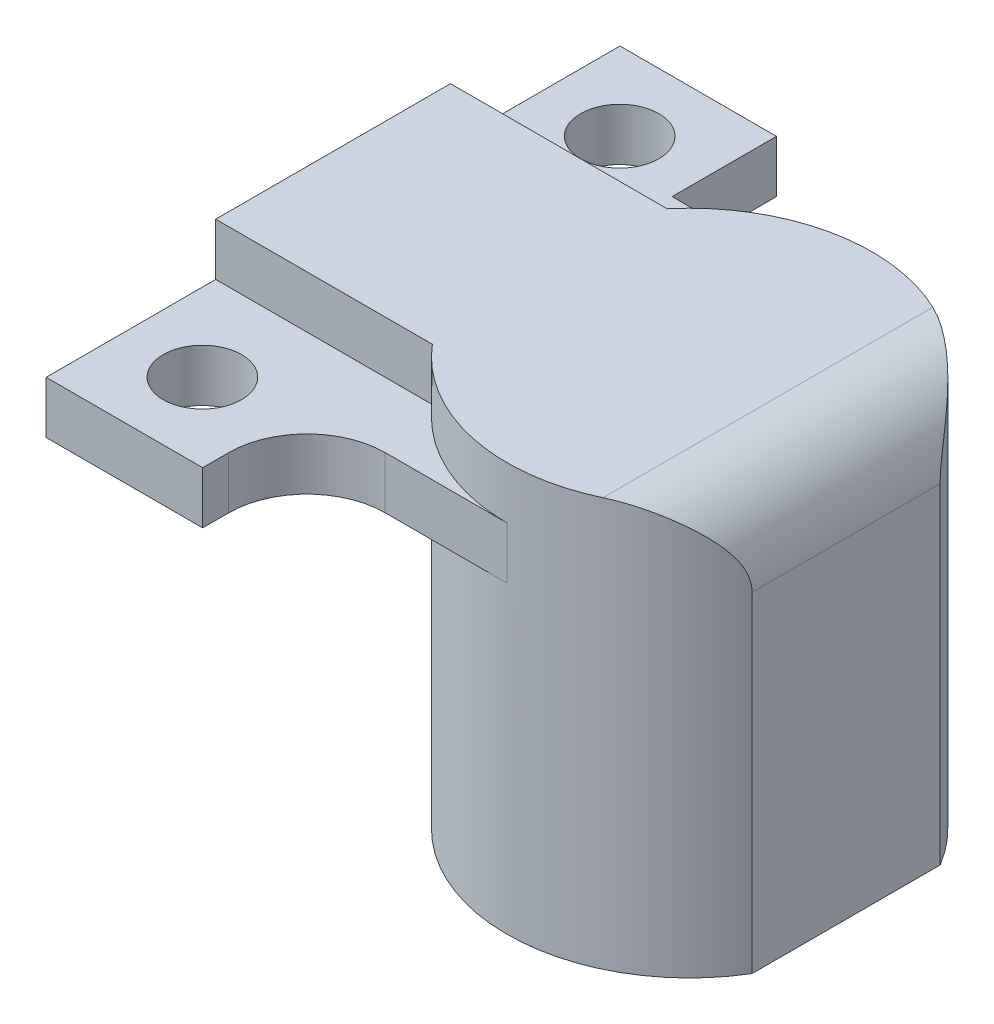
SolidWorks part; units mm, degrees
material "Copper"
ref_plane "Front Plane" through (0, 0, 0) normal (0, 0, 1) x (1, 0, 0)
ref_plane "Top Plane" through (0, 0, 0) normal (0, 1, 0) x (1, 0, 0)
ref_plane "Right Plane" through (0, 0, 0) normal (1, 0, 0) x (0, 0, -1)
sketch "Sketch1" plane through (0, 0, 0) normal (0, 1, 0) x (1, 0, 0)
  circle A0 centre (0, 0) radius 5.2
  circle A1 centre (0, 0) radius 7
  dimension "D1" = 10.4
  dimension "D2" = 14
extrude "Boss-Extrude1" add sketch "Sketch1" along normal blind 15.66
sketch "Sketch2" plane through (0, 15.66, 0) normal (0, 1, 0) x (1, 0, 0)
  line L0 (0, 0) -> (-6.5789, 0) construction
  line L1 (0, 5.2) -> (0, 7)
  line L2 (-13.67, -7) -> (0, -7)
  line L3 (-13.67, -7) -> (-13.67, 7)
  line L4 (-13.67, 7) -> (0, 7)
  line L5 (0, -7) -> (0, -5.2)
  line L6 (-13.67, -7) -> (0, 7) construction
  line L7 (-13.67, 7) -> (0, -7) construction
  line L8 (-7.67, 7) -> (-7.67, 11)
  line L9 (-13.67, -7) -> (-7.67, -7)
  line L10 (-13.67, -7) -> (-13.67, -11)
  line L11 (-13.67, -11) -> (-7.67, -11)
  line L12 (-7.67, -7) -> (-7.67, -11)
  line L13 (-13.67, 11) -> (-7.67, 11)
  line L14 (-13.67, 7) -> (-13.67, 11)
  line L15 (-13.67, 7) -> (-7.67, 7)
  circle A0 centre (0, 0) radius 7 construction
  circle A1 centre (0, 0) radius 5.2 construction
  arc A2 (0, 5.2) -> (0, -5.2) centre (0, 0) ccw
  point P3 (-6.835, 0)
  circle M6 centre (0, 0) radius 7
  dimension "D1" = 4
  dimension "D2" = 13.67
  dimension "D3" = 6
extrude "Boss-Extrude2" add sketch "Sketch2" against normal blind 4 contours L12 L2 L10 L11 | L4 L3 L2 M6 | L15 L8 L13 L14 region at (-9.4345, 15.66, 0) region at (-10.67, 15.66, 9)
extrude "Cut-Extrude2" cut sketch "Sketch2<3>" against normal blind 2 contours L4 L3 L2 M6 | L14 L4 L8 L13 | L12 L2 L10 L11 region at (-9.4345, 15.66, 0) region at (-10.67, 15.66, -9) region at (-10.67, 15.66, 9)
sketch "Sketch2<3>" plane through (0, 15.66, 0) normal (0, 1, 0) x (1, 0, 0) same geometry as "Sketch2"
sketch "Sketch4" plane through (0, 11.66, 0) normal (0, -1, 0) x (1, 0, 0)
  line L0 (-13.67, 8) -> (-7.899, 8) construction
  line L2 (-13.67, -11) -> (-13.67, 11) construction
  line L3 (0, 0) -> (-21.2142, 0) construction
  line L4 (-13.67, 11) -> (-7.67, 11) construction
  circle A0 centre (-10.68, 8) radius 1.5
  circle A1 centre (-10.68, -8) radius 1.5
  dimension "D1" = 3
  dimension "D2" = 2.99
  dimension "D3" = 3
extrude "Cut-Extrude1" cut sketch "Sketch4" against normal blind 10 contours A1 | A0 region at (-10.68, 11.66, -8)
fillet "Fillet7" radius 3 1 edges at (-7.67, 12.66, 7) type face fillet first side face at (-3.835, 12.66, 7) second side face at (-7.67, 12.66, 9)
sketch "Sketch5" plane through (0, 15.66, 0) normal (0, 1, 0) x (1, 0, 0)
  circle A0 centre (0, 0) radius 5.2 construction
  circle A1 centre (0, 0) radius 5.2
extrude "Boss-Extrude3" add sketch "Sketch5" against normal blind 1
sketch "Sketch6" plane through (0, 0, 0) normal (0, -1, 0) x (1, 0, 0)
  line L0 (6, -3.6056) -> (6, 3.6056)
  circle A0 centre (0, 0) radius 7 construction
  arc A3 (6, -3.6056) -> (6, 3.6056) centre (0, 0) ccw
  point P5 (7, 0)
  dimension "D1" = 1
extrude "Cut-Extrude3" cut sketch "Sketch6" along direction (0, 1, 0) on the side against the normal up to next
fillet "Fillet8" radius 3 1 edges at (6, 15.66, 0) type face fillet first side face at (6, 7.83, 0) second side face at (-0.5, 15.66, 0)
sketch "Sketch7" plane through (0, 13.66, 0) normal (0, 1, 0) x (1, 0, 0)
  line L1 (-13.67, -11) -> (-13.67, 11) construction
  line L2 (-13.67, 4.5) -> (-13.67, -4.5)
  line L3 (-13.67, -4.5) -> (-5.3619, -4.5)
  line L4 (-13.67, 4.5) -> (-5.3619, 4.5)
  arc A0 (3, 6.3246) -> (3, -6.3246) centre (0, 0) ccw construction
  arc A1 (-5.3619, 4.5) -> (-5.3619, -4.5) centre (0, 0) ccw
extrude "Boss-Extrude4" add sketch "Sketch7" along normal blind 2
